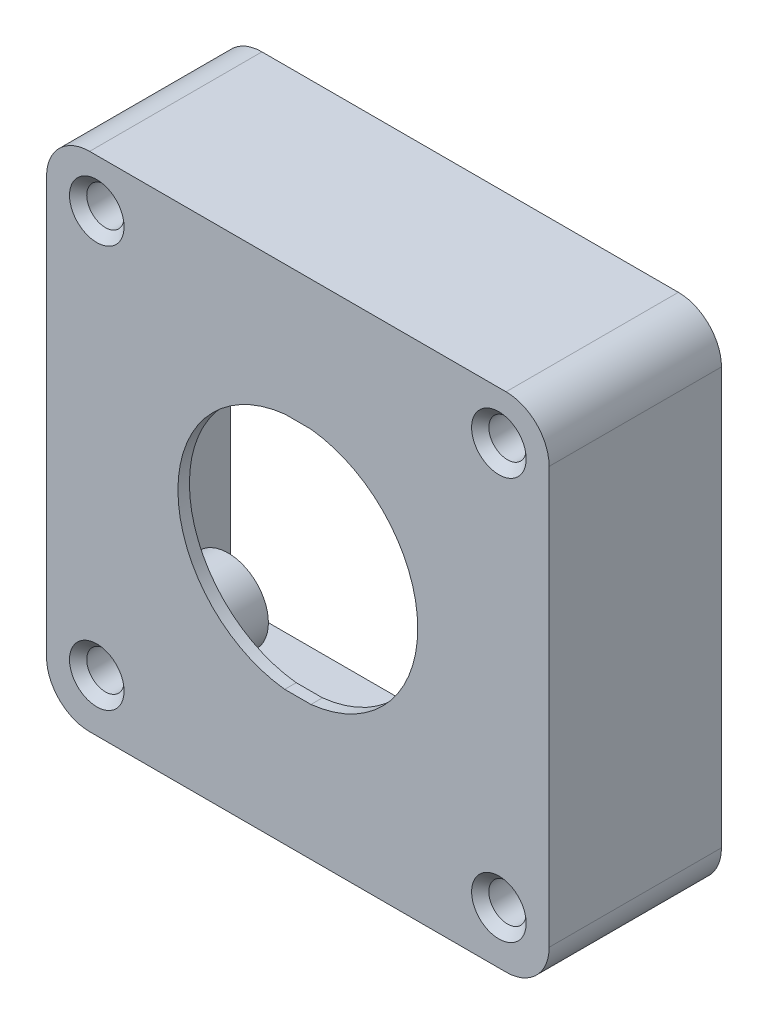
SolidWorks part; units mm, degrees
ref_plane "Alzado" through (0, 0, 0) normal (0, 0, 1) x (1, 0, 0)
ref_plane "Planta" through (0, 0, 0) normal (0, 1, 0) x (1, 0, 0)
ref_plane "Vista lateral" through (0, 0, 0) normal (1, 0, 0) x (0, 0, -1)
sketch "Croquis2" plane through (0, 0, 0) normal (0, 0, 1) x (1, 0, 0)
  line L1 (-17.5, -17.5) -> (17.5, -17.5)
  line L2 (-17.5, -17.5) -> (-17.5, 17.5)
  line L3 (-17.5, 17.5) -> (17.5, 17.5)
  line L4 (17.5, -17.5) -> (17.5, 17.5)
  line L5 (0, 17.5) -> (0, -17.5) construction
  line L6 (-17.5, 0) -> (17.5, 0) construction
  point P0 (0, 0)
  dimension "D1" = 35
  dimension "D2" = 35
extrude "Saliente-Extruir1" add sketch "Croquis2" along normal blind 12
fillet "Redondeo1" radius 3 4 edges at (-17.5, 17.5, 6) (-17.5, -17.5, 6) (17.5, -17.5, 6) (17.5, 17.5, 6)
shell "Vaciado1" thickness 0.8 removed face at (0, 0, 0)
sketch "Croquis5" plane through (0, 0, 12) normal (0, 0, 1) x (1, 0, 0)
  line L0 (-0.8846, 7.95) -> (0.8846, 7.95) construction
  line L1 (-0.8846, -7.65) -> (0.8846, -7.65) construction
  line L2 (-0.9124, 8.45) -> (0.9124, 8.45)
  line L3 (-0.9124, -8.15) -> (0.9124, -8.15)
  arc A0 (0.9124, -8.15) -> (0.9124, 8.45) centre (0, 0.15) ccw
  arc A1 (-0.9124, 8.45) -> (-0.9124, -8.15) centre (0, 0.15) ccw
  arc A8 (0.8846, -7.65) -> (0.8846, 7.95) centre (0, 0.15) ccw construction
  arc A12 (-0.8846, 7.95) -> (-0.8846, -7.65) centre (0, 0.15) ccw construction
  dimension "D1" = 0.5
extrude "Cortar-Extruir3" cut sketch "Croquis5" against normal through all
sketch "Croquis6" plane through (0, 0, 12) normal (0, 0, 1) x (1, 0, 0)
  circle A4 centre (14, -13.85) radius 1 construction
  circle A5 centre (14, 14.15) radius 1 construction
  circle A6 centre (-14, -13.85) radius 1 construction
  circle A7 centre (-14, 14.15) radius 1 construction
  circle A8 centre (-14, 14.15) radius 1.3
  circle A9 centre (14, 14.15) radius 1.3
  circle A10 centre (14, -13.85) radius 1.3
  circle A11 centre (-14, -13.85) radius 1.3
  dimension "D1" = 0.3
extrude "Cortar-Extruir4" cut sketch "Croquis6" against normal through all
chamfer "Chaflán3" distance 0.6 angle 45 4 edges at (-12.7, -13.85, 12) (15.3, -13.85, 12) (15.3, 14.15, 12) (-12.7, 14.15, 12)
sketch "Croquis7" plane through (0, 0, 11.2) normal (0, 0, -1) x (-1, 0, 0)
  circle A0 centre (-14, -13.85) radius 1.3 construction
  circle A1 centre (14, -13.85) radius 1.3 construction
  circle A2 centre (14, 14.15) radius 1.3 construction
  circle A3 centre (-14, 14.15) radius 1.3 construction
  circle A4 centre (-14, -13.85) radius 1.3
  circle A5 centre (14, -13.85) radius 1.3
  circle A6 centre (14, 14.15) radius 1.3
  circle A7 centre (-14, 14.15) radius 1.3
  circle A8 centre (-14, 14.15) radius 2.8
  circle A9 centre (14, 14.15) radius 2.8
  circle A10 centre (14, -13.85) radius 2.8
  circle A11 centre (-14, -13.85) radius 2.8
  dimension "D1" = 1.5
extrude "Saliente-Extruir2" add sketch "Croquis7" along normal blind 8.35
